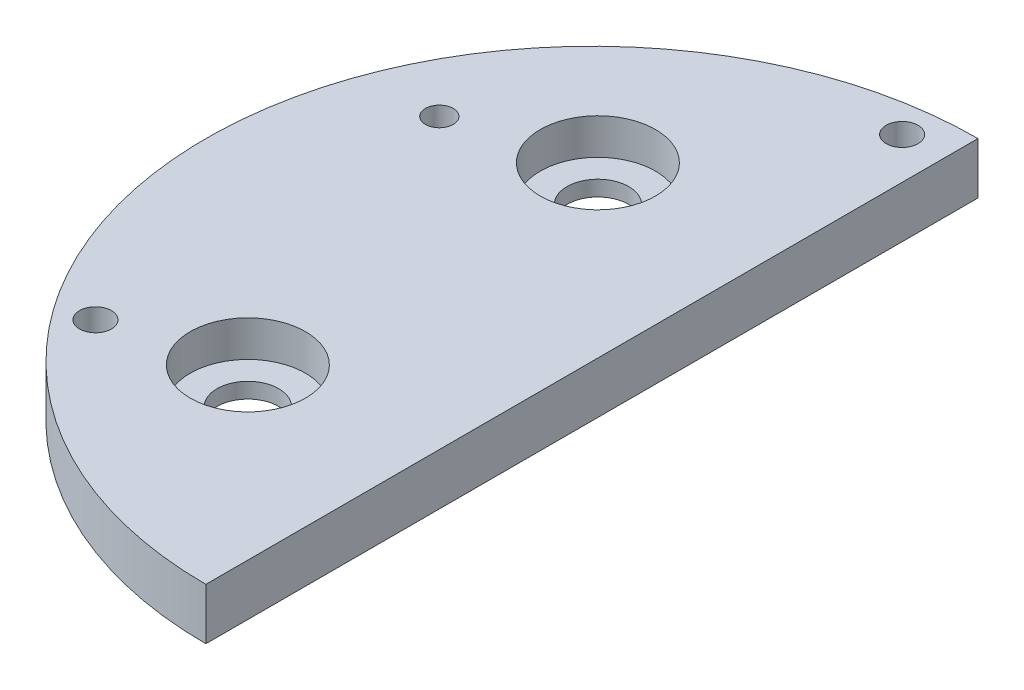
SolidWorks part; units mm, degrees
ref_plane "Ebene vorne" through (0, 0, 0) normal (0, 0, 1) x (1, 0, 0)
ref_plane "Ebene oben" through (0, 0, 0) normal (0, 1, 0) x (1, 0, 0)
ref_plane "Ebene rechts" through (0, 0, 0) normal (1, 0, 0) x (0, 0, -1)
sketch "Skizze1" plane through (0, 0, 0) normal (0, 1, 0) x (1, 0, 0)
  line L0 (0, 0) -> (0, -75)
  line L1 (0, -37.5) -> (-48.465, -37.5) construction
  arc A1 (0, -75) -> (0, 0) centre (0, -37.5) cw
  dimension "D1" = 75
extrude "Aufsatz-Linear austragen1" add sketch "Skizze1" along normal blind 5
sketch "Skizze11" plane through (0, 5, 0) normal (0, 1, 0) x (1, 0, 0)
  line L0 (0, -37.5) -> (-37.5, -37.5) construction
  line L1 (0, -75) -> (0, 0) construction
  line L2 (-16.42, -37.5) -> (-16.42, -1.2821) construction
  line L3 (-16.42, -1.2821) -> (-16.42, -74.2151) construction
  arc A0 (0, 0) -> (0, -75) centre (0, -37.5) ccw construction
  circle A1 centre (-16.42, -20.5) radius 5.6
  circle A2 centre (-16.42, -54.5) radius 5.6
  dimension "D1" = 17
  dimension "D2" = 11.2
  dimension "D4" = 11.2
  dimension "D5" = 17
  dimension "D3" = 16.42
extrude "Schnitt-Linear austragen1" cut sketch "Skizze11" against normal blind 3.5
sketch "Skizze12" plane through (0, 1.5, 0) normal (0, 1, 0) x (1, 0, 0)
  circle A0 centre (-16.42, -54.5) radius 3
  circle A1 centre (-16.42, -20.5) radius 3
extrude "Schnitt-Linear austragen2" cut sketch "Skizze12" against normal blind 1.5
sketch "Skizze13" [suppressed] plane through (0, 5, 0) normal (0, 1, 0) x (1, 0, 0)
  line L0 (-7.0858, -11.2984) -> (-5, -11.2984)
  line L1 (-5, -8.1916) -> (-7.0858, -8.1916)
  line L2 (-7.0858, -8.1916) -> (-7.0858, -11.2984)
  line L3 (-5, -8.1916) -> (-5, -11.2984)
  line L4 (0, -75) -> (0, 0) construction
  dimension "D1" = 3.1068
  dimension "D2" = 2.0858
  dimension "D3" = 5
extrude "Aufsatz-Linear austragen2" [suppressed] add sketch "Skizze13" along normal blind 7
sketch "Skizze14" [suppressed] plane through (0, 12, 0) normal (0, 1, 0) x (1, 0, 0)
  line L0 (-5, -8.1916) -> (-5, -11.2984)
  line L1 (-5, -11.2984) -> (-14.09, -11.2984)
  line L2 (-14.09, -11.2984) -> (-14.09, -8.1916)
  line L3 (-14.09, -8.1916) -> (-5, -8.1916)
  dimension "D1" = 9.09
extrude "Aufsatz-Linear austragen3" [suppressed] add sketch "Skizze14" along normal blind 2
sketch "Skizze18" [suppressed] plane through (0, 0, 8.1916) normal (0, 0, -1) x (-1, 0, 0)
  line L0 (7.0858, 4.9958) -> (14.09, 12)
  line L2 (14.09, 12) -> (7.0858, 12)
  line L3 (7.0858, 12) -> (7.0858, 4.9958)
  line L4 (7.0858, 12) -> (7.0858, 5) construction
  dimension "D1" = 45
extrude "Aufsatz-Linear austragen5" [suppressed] add sketch "Skizze18" against normal blind 3.1
fillet "Verrundung2" [suppressed] radius 1
sketch "Skizze16" [suppressed] plane through (0, 14, 0) normal (0, 1, 0) x (1, 0, 0)
  line L0 (-14.09, -11.2984) -> (-10.89, -11.2984)
  line L1 (-14.09, -11.2984) -> (-5, -11.2984) construction
  arc A0 (-10.89, -11.2984) -> (-14.09, -11.2984) centre (-12.49, -11.2984) ccw
  dimension "D1" = 3.2
extrude "Schnitt-Linear austragen3" [suppressed] cut sketch "Skizze16" against normal blind 5.5
sketch "Skizze17" [suppressed] plane through (0, 5, 0) normal (0, 1, 0) x (1, 0, 0)
  circle A0 centre (-3.3122, -19.9751) radius 1.35
  dimension "D1" = 2.7
fillet "Verrundung3" [suppressed] radius 0.5
fillet "Verrundung4" [suppressed] radius 2
sketch "Skizze20" plane through (0, 5, 0) normal (0, 1, 0) x (1, 0, 0)
  circle A0 centre (-4.0289, -3.3441) radius 1.55
  dimension "D1" = 3.1
extrude "Schnitt-Linear austragen4" cut sketch "Skizze20" against normal through all
sketch "Skizze21" plane through (0, 5, 0) normal (0, 1, 0) x (1, 0, 0)
  circle A0 centre (-27.6128, -58.1085) radius 1.55
  dimension "D1" = 3.1
extrude "Schnitt-Linear austragen5" cut sketch "Skizze21" against normal through all
sketch "Skizze22" plane through (0, 5, 0) normal (0, 1, 0) x (1, 0, 0)
  circle A0 centre (-28.0196, -24.3022) radius 1.35
  dimension "D1" = 2.7
extrude "Schnitt-Linear austragen6" cut sketch "Skizze22" against normal blind 3.5
extrude "Schnitt-Linear austragen7" [suppressed] cut sketch "Skizze17" against normal blind 3.5
